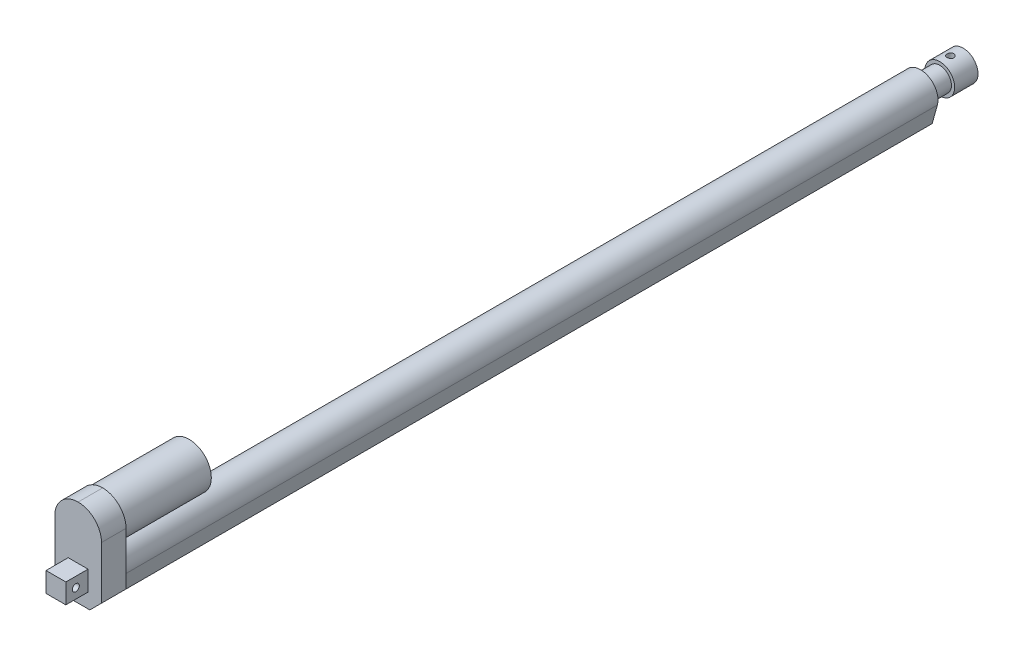
SolidWorks part; units mm, degrees
ref_plane "前视基准面" through (0, 0, 0) normal (0, 0, 1) x (1, 0, 0)
ref_plane "上视基准面" through (0, 0, 0) normal (0, 1, 0) x (1, 0, 0)
ref_plane "右视基准面" through (0, 0, 0) normal (1, 0, 0) x (0, 0, -1)
other "Configuration Table"
sketch "草图1" plane through (0, 0, 0) normal (0, 0, 1) x (1, 0, 0)
  line L1 (-20, 37.5) -> (20, 37.5)
  line L2 (-20, 37.5) -> (-20, -37.5)
  line L3 (-20, -37.5) -> (20, -37.5)
  line L4 (20, 37.5) -> (20, -37.5)
  dimension "D1" = 75
  dimension "D2" = 40
  dimension "D3" = 20
  dimension "D4" = 37.5
extrude "凸台-拉伸1" add sketch "草图1" along normal blind 21
fillet "圆角1" radius 20 2 edges at (-20, 37.5, 10.5) (20, 37.5, 10.5)
chamfer "倒角1" distance 10 angle 45 2 edges at (-20, -37.5, 10.5) (20, -37.5, 10.5)
sketch "草图2" plane through (0, 0, 0) normal (0, 0, -1) x (-1, 0, 0)
  line L0 (10, -37.5) -> (-10, -37.5) construction
  line L1 (-10, -37.5) -> (10, -37.5)
  line L2 (10, -37.5) -> (14.4499, -21.5251)
  line L3 (-10, -37.5) -> (-14.4499, -21.5251)
  arc A0 (14.4499, -21.5251) -> (-14.4499, -21.5251) centre (0, -17.5) ccw
  circle A1 centre (0, -17.5) radius 20 construction
  dimension "D1" = 30
  dimension "D2" = 40
extrude "凸台-拉伸2" add sketch "草图2" along normal blind 700
sketch "草图3" plane through (0, 0, 0) normal (0, 0, -1) x (-1, 0, 0)
  circle A0 centre (0, 17.5) radius 19
  arc A1 (20, 17.5) -> (0, 37.5) centre (0, 17.5) ccw construction
  dimension "D1" = 38
extrude "凸台-拉伸4" add sketch "草图3" along normal blind 74
sketch "草图4" plane through (0, 0, 21) normal (0, 0, 1) x (1, 0, 0)
  line L0 (-10, -37.5) -> (10, -37.5) construction
  line L1 (-8.5, -8) -> (8.5, -8)
  line L2 (-8.5, -8) -> (-8.5, -25)
  line L3 (-8.5, -25) -> (8.5, -25)
  line L4 (8.5, -8) -> (8.5, -25)
  dimension "D1" = 17
  dimension "D2" = 8.5
  dimension "D3" = 12.5
extrude "凸台-拉伸5" add sketch "草图4" along normal blind 19
sketch "草图5" plane through (-8.5, 0, 0) normal (-1, 0, 0) x (0, 0, 1)
  line L0 (40, -8) -> (40, -25) construction
  line L1 (40, -8) -> (21, -8) construction
  circle A0 centre (31.5, -16.5) radius 3
  dimension "D1" = 8.5
  dimension "D2" = 6
  dimension "D3" = 8.5
extrude "切除-拉伸1" cut sketch "草图5" against normal blind 19
sketch "草图6" plane through (0, 0, -700) normal (0, 0, -1) x (-1, 0, 0)
  circle A0 centre (0, -17.5) radius 10
  dimension "D1" = 20
extrude "凸台-拉伸6" add sketch "草图6" along normal blind 16.5
sketch "草图7" plane through (0, 0, -716.5) normal (0, 0, -1) x (-1, 0, 0)
  circle A0 centre (0, -17.5) radius 12.75
  dimension "D1" = 25.5
extrude "凸台-拉伸7" add sketch "草图7" along normal blind 20
sketch "草图9" plane through (0, -37.5, 0) normal (0, -1, 0) x (1, 0, 0)
  line L0 (-12.75, -736.5) -> (12.75, -736.5) construction
  line L1 (-12.75, -716.5) -> (-12.75, -736.5) construction
  circle A0 centre (0, -725.5) radius 2.9
  dimension "D1" = 5.8
  dimension "D2" = 11
  dimension "D3" = 12.75
extrude "切除-拉伸2" cut sketch "草图9" against normal through all
